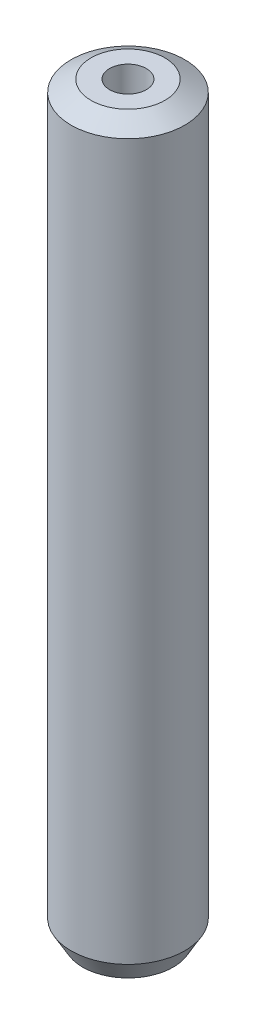
SolidWorks part; units mm, degrees
ref_plane "Front Plane" through (0, 0, 0) normal (0, 0, 1) x (1, 0, 0)
ref_plane "Top Plane" through (0, 0, 0) normal (0, 1, 0) x (1, 0, 0)
ref_plane "Right Plane" through (0, 0, 0) normal (1, 0, 0) x (0, 0, -1)
sketch "Sketch1" plane through (0, 0, 0) normal (0, 1, 0) x (1, 0, 0)
  circle A0 centre (0, 0) radius 20
  dimension "SHAFT_OD" = 40
extrude "Boss-Extrude1" add sketch "Sketch1" along normal blind 262.7239
sketch "Sketch2" plane through (0, 0, 0) normal (0, 1, 0) x (1, 0, 0)
  circle A0 centre (0, 0) radius 6.4665
  dimension "BORE_D" = 12.9331
extrude "Cut-Extrude1" cut sketch "Sketch2" along normal through all
chamfer "Chamfer1" distance 4.047 angle 60 2 edges at (0, 262.7239, 20) (0, 0, 20) first distance on face at (0, 262.7239, 20) first distance on face at (0, 0, 6.4665)
